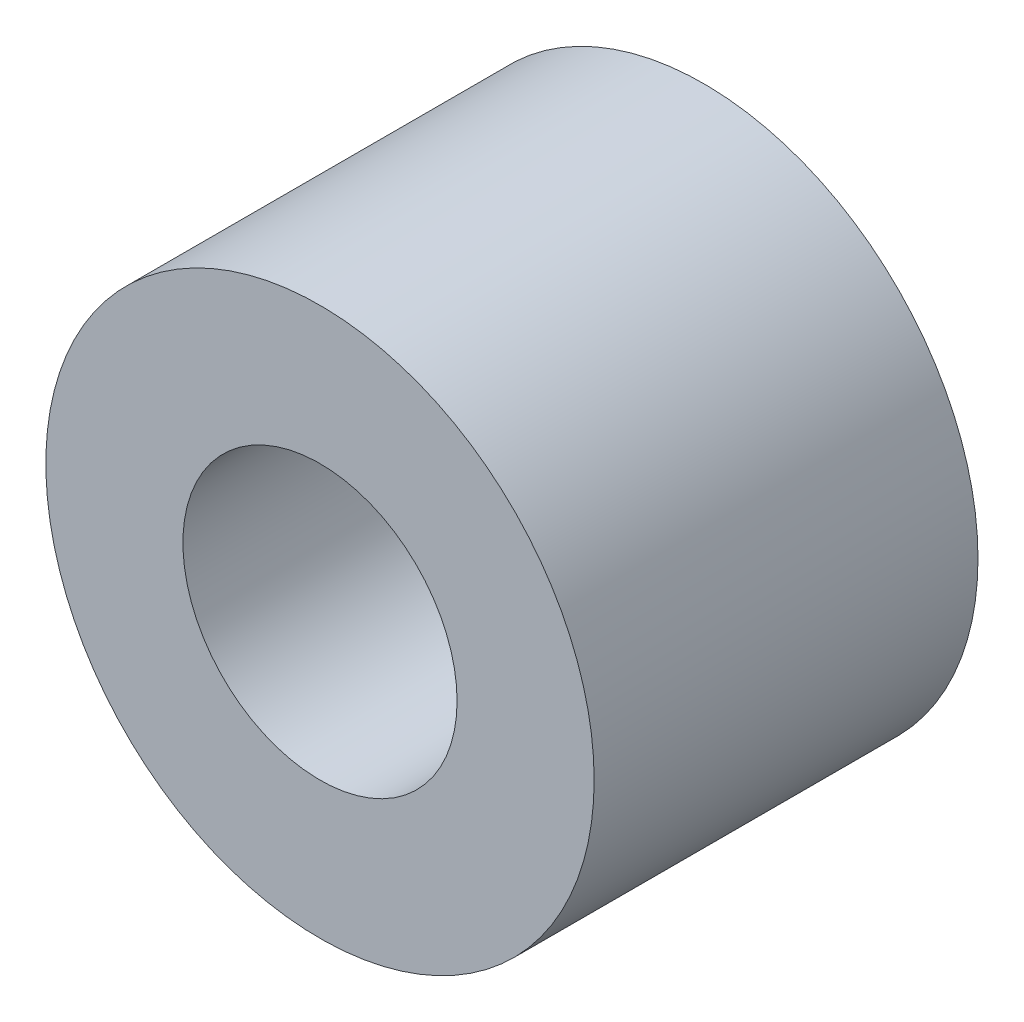
SolidWorks part; units mm, degrees
ref_plane "Alzado" through (0, 0, 0) normal (0, 0, 1) x (1, 0, 0)
ref_plane "Planta" through (0, 0, 0) normal (0, 1, 0) x (1, 0, 0)
ref_plane "Vista lateral" through (0, 0, 0) normal (1, 0, 0) x (0, 0, -1)
sketch "Croquis1" plane through (0, 0, 0) normal (0, 0, 1) x (1, 0, 0)
  circle A2 centre (54.9, 15.2) radius 2.5
  circle A3 centre (54.9, 15.2) radius 5
  dimension "D1" = 10
  dimension "D2" = 5
extrude "Saliente-Extruir1" add sketch "Croquis1" along normal blind 7
